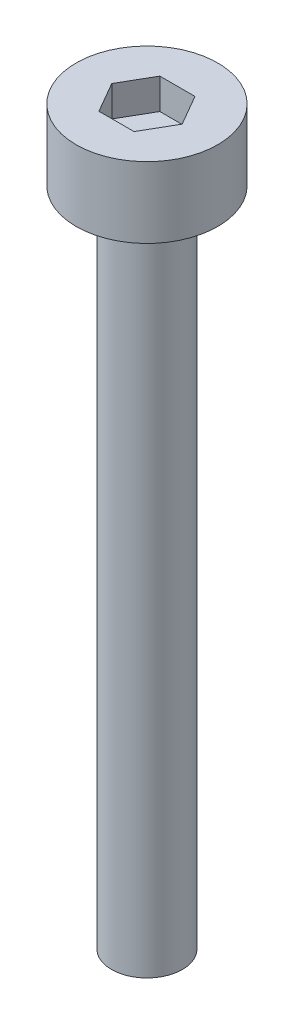
SolidWorks part; units mm, degrees
ref_plane "Front Plane" through (0, 0, 0) normal (0, 0, 1) x (1, 0, 0)
ref_plane "Top Plane" through (0, 0, 0) normal (0, 1, 0) x (1, 0, 0)
ref_plane "Right Plane" through (0, 0, 0) normal (1, 0, 0) x (0, 0, -1)
sketch "Sketch1" plane through (0, 0, 0) normal (0, 1, 0) x (1, 0, 0)
  circle A0 centre (0, 0) radius 1.5
  dimension "D1" = 3
extrude "ScrewShaft" add sketch "Sketch1" along normal blind 28
sketch "Sketch2" plane through (0, 28, 0) normal (0, 1, 0) x (1, 0, 0)
  circle A0 centre (0, 0) radius 3
  dimension "D1" = 6
extrude "Boss-Extrude2" add sketch "Sketch2" along normal blind 3
sketch "Sketch3" plane through (0, 31, 0) normal (0, 1, 0) x (1, 0, 0)
  line L0 (0, 0) -> (0, 1.29) construction
  line L1 (1.4896, 0) -> (0.7448, 1.29)
  line L2 (0.7448, 1.29) -> (-0.7448, 1.29)
  line L3 (-0.7448, 1.29) -> (-1.4896, 0)
  line L4 (-1.4896, 0) -> (-0.7448, -1.29)
  line L5 (-0.7448, -1.29) -> (0.7448, -1.29)
  line L6 (0.7448, -1.29) -> (1.4896, 0)
  circle A0 centre (0, 0) radius 1.29 construction
  dimension "D1" = 2.58
extrude "Cut-Extrude1" cut sketch "Sketch3" against normal blind 1.3
equation "\"X-ROD-SPACING\"=45"
equation "\"Y-ROD-SPACING\"=75"
equation "\"Z-ROD-SPACING\"=17.5"
equation "\"Y-BED-OFFSET\"=2"
equation "\"Y-BED-ROD-INSET\"=3.5"
equation "\"T-SLOT-NUT-FILLET-RADIUS\"=0.25"
equation "\"T-SLOT-SCREW-SHAFT-RADIUS\"=1.75"
equation "\"T-SLOT-SCREW-SHAFT-CUTOUT-LENGTH\"=10.5"
equation "\"T-SLOT-NUT-DEPTH\"=4.2"
equation "\"T-SLOT-NUT-WIDTH\"=3"
equation "\"T-SLOT-NUT-END-DISTANCE\"=8"
equation "\"ACRYLIC-THICKNESS\"=10"
equation "\"ACRYLIC-THICKNESS2\"=4.5"
equation "\"ACRYLIC-TAB-CUTOUT-SIZE\"=\"ACRYLIC-THICKNESS\"+\"ACRYLIC-TAB-TOLERANCE\"*2"
equation "\"ACRYLIC-TAB-WIDTH\"=\"ACRYLIC-THICKNESS\""
equation "\"ACRYLIC-M3-HOLE\"=3.2"
equation "\"SMOOTHROD-CAP-SCREW-DISTANCE\"=20"
equation "\"FRAME-WIDTH-INNER\"=370"
equation "\"NEMA17-HOLE-SPACING\"=31"
equation "\"NEMA17-CENTRAL-CUTOUT\"=22.5"
equation "\"Z-BRACKET-REACH\"=55"
equation "\"TOP-BRACKET-SPACING\"=40"
equation "\"SMOOTHROD-X-LENGTH\"=350"
equation "\"SMOOTHROD-Y-LENGTH\"=350"
equation "\"SMOOTHROD-Z-LENGTH\"=350"
equation "\"SMOOTHROD-TIGHTENING-HEADROOM\"=1"
equation "\"LEADSCREW-Z-LENGTH\"=300"
equation "\"SCREW-LENGTH-FRAME\"=\"ACRYLIC-THICKNESS\" + 10"
equation "\"SCREW-HEAD-RADIUS\"=6"
equation "\"PRINTED-X-SMOOTHROD-DIAMETER\"=8.2"
equation "\"PRINTED-X-SMOOTHROD-CUTOUT\"=10"
equation "\"PRINTED-X-BASE-HEIGHT\"=10"
equation "\"PRINTED-LM8UU-CUTOUT-SIZE\"=16"
equation "\"PRINTED-LM8UU-CUTOUT-LENGTH\"=24.5"
equation "\"PRINTED-X-IDLER-HEIGHT\"=16"
equation "\"PSU-MOUNTING-WIDTH\"=95"
equation "\"PSU-MOUNTING-HEIGHT\"=177"
equation "\"D1@ScrewShaft\"=\"SCREW-LENGTH-EXTRUDER\""
equation "\"D1@Sketch2\"=\"SCREW-HEAD-RADIUS\""
equation "\"Y-BED-SCREW-SPACING\"=209"
equation "\"Y-BED-SCREW-CUTOUT-SLOT-HEIGHT\"=1"
equation "\"Z-ROD-INSET\"=16"
equation "\"SCREW-LENGTH-MOTOR\"=\"ACRYLIC-THICKNESS\" + 5"
equation "\"SCREW-LENGTH-EXTRUDER\"=28"
equation "\"Y-BELT-TO-ROD-DISTANCE\"=20"
equation "\"SPOOL-HOLDER-ROD-SPACING\"=150"
equation "\"ACRYLIC-X-CARRIAGE-WIDTH\"=55"
equation "\"ACRYLIC-X-CARRIAGE-HEIGHT\"=75"
equation "\"ACRYLIC-X-CARRIAGE-CENTER-TAB-SPACING\"=14"
